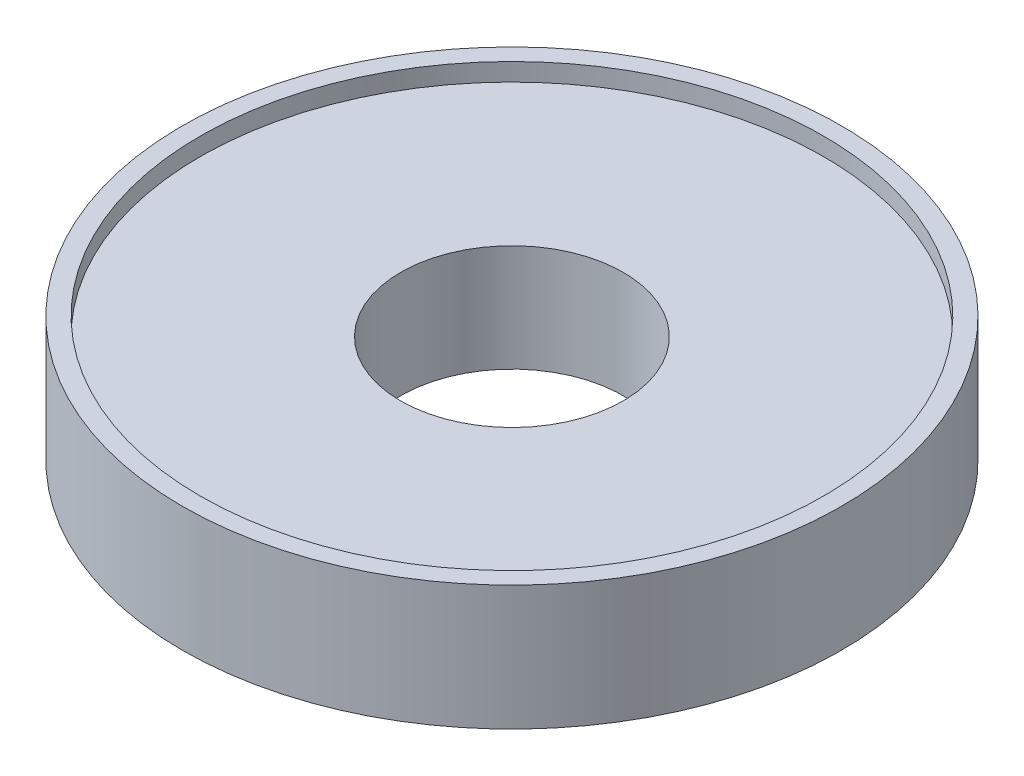
SolidWorks part; units mm, degrees
ref_plane "Front Plane" through (0, 0, 0) normal (0, 0, 1) x (1, 0, 0)
ref_plane "Top Plane" through (0, 0, 0) normal (0, 1, 0) x (1, 0, 0)
ref_plane "Right Plane" through (0, 0, 0) normal (1, 0, 0) x (0, 0, -1)
sketch "Sketch1" plane through (0, 0, 0) normal (0, 1, 0) x (1, 0, 0)
  circle A0 centre (0, 0) radius 18.5
  circle A1 centre (0, 0) radius 17.5 construction
  dimension "D1" = 35
  dimension "D2" = 1
extrude "Boss-Extrude1" add sketch "Sketch1" along normal blind 6
sketch "Sketch2" plane through (0, 6, 0) normal (0, 1, 0) x (1, 0, 0)
  circle A0 centre (0, 0) radius 17.5 construction
  circle A1 centre (0, 0) radius 17.5
  circle A2 centre (0, 0) radius 18.5 construction
  circle A3 centre (0, 0) radius 18.5
extrude "Boss-Extrude2" add sketch "Sketch2" along normal blind 1
hole_wizard "M14x1.5 Tapped Hole1" positions "Sketch3" profile "Sketch4" tap size "M14x1.5" standard "ANSI Metric" end condition through all
sketch "Sketch3" plane through (0, 6, 0) normal (0, 1, 0) x (1, 0, 0)
  point P0 (0, 0)
sketch "Sketch4" plane through (0, 6, 0) normal (1, 0, 0) x (0, 0, 1)
  line L0 (0, 0) -> (0, 6)
  line L1 (0, 6) -> (6.25, 6)
  line L2 (6.25, 6) -> (6.25, 0)
  line L5 (6.25, 0) -> (0, 0)
  line L11 (0, -6.35) -> (0, 107.95) construction
  dimension "Thru Tap Drill Dia." = 12.5
  dimension "Thru Tap Drill Depth" = 6
sketch "Sketch5" plane through (0, 0, 0) normal (0, -1, 0) x (1, 0, 0)
  line L1 (10.6066, -10.6066) -> (-10.6066, -10.6066) construction
  line L2 (10.6066, -10.6066) -> (10.6066, 10.6066) construction
  line L3 (10.6066, 10.6066) -> (-10.6066, 10.6066) construction
  line L4 (-10.6066, -10.6066) -> (-10.6066, 10.6066) construction
  line L5 (10.6066, -10.6066) -> (-10.6066, 10.6066) construction
  line L6 (10.6066, 10.6066) -> (-10.6066, -10.6066) construction
  circle A0 centre (-10.6066, 10.6066) radius 2.25
  circle A1 centre (10.6066, 10.6066) radius 2.25
  circle A2 centre (10.6066, -10.6066) radius 2.25
  circle A3 centre (-10.6066, -10.6066) radius 2.25
  point P0 (0, 0)
  dimension "D2" = 4.5
  dimension "D1" = 30
extrude "Cut-Extrude1" cut sketch "Sketch5" against normal blind 4
